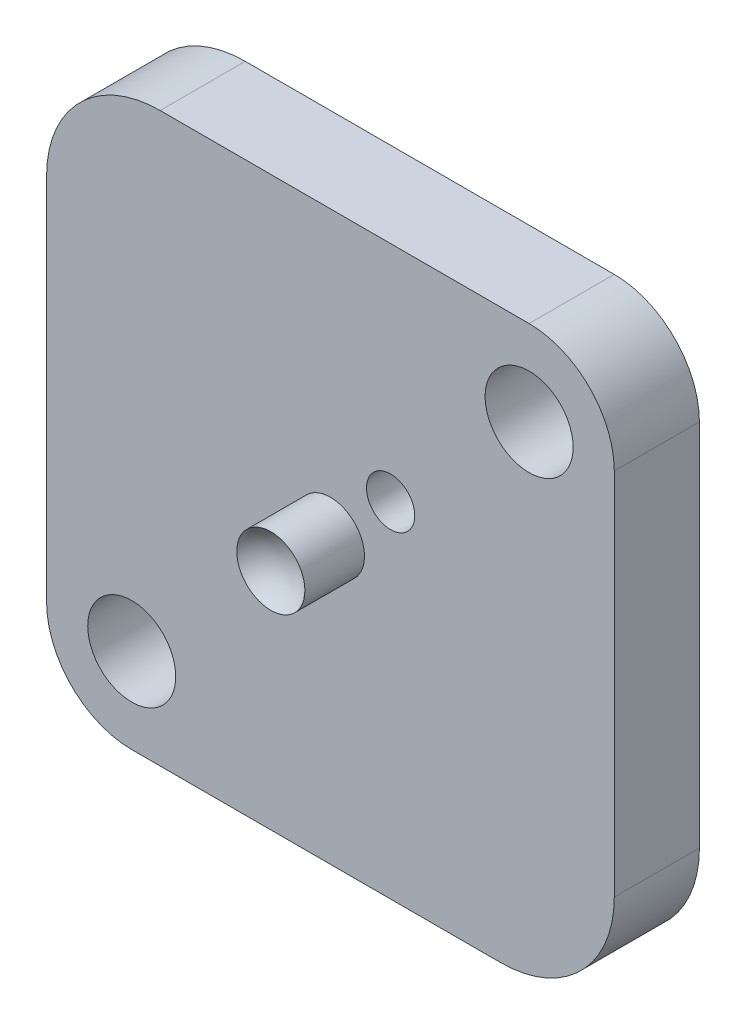
SolidWorks part; units mm, degrees
ref_plane "Front Plane" through (0, 0, 0) normal (0, 0, 1) x (1, 0, 0)
ref_plane "Top Plane" through (0, 0, 0) normal (0, 1, 0) x (1, 0, 0)
ref_plane "Right Plane" through (0, 0, 0) normal (1, 0, 0) x (0, 0, -1)
sketch "Sketch1" plane through (0, 0, 0) normal (0, 0, 1) x (1, 0, 0)
  line L1 (50, -50) -> (-50, -50)
  line L2 (50, -50) -> (50, 50)
  line L3 (50, 50) -> (-50, 50)
  line L4 (-50, -50) -> (-50, 50)
  line L5 (50, -50) -> (-50, 50) construction
  line L6 (50, 50) -> (-50, -50) construction
  point P0 (0, 0)
  dimension "D1" = 100
  dimension "D2" = 100
extrude "Boss-Extrude1" add sketch "Sketch1" along normal blind 15
sketch "Sketch2" plane through (0, 0, 15) normal (0, 0, 1) x (1, 0, 0)
  line L2 (50, -50) -> (50, 50) construction
  line L3 (50, 50) -> (-50, 50) construction
  line L4 (-50, 50) -> (50, -50) construction
  circle A0 centre (35, 35) radius 7.75
  circle A1 centre (-35, -35) radius 7.75
  dimension "D1" = 15.5
  dimension "D2" = 15
  dimension "D3" = 15
extrude "Cut-Extrude1" cut sketch "Sketch2" against normal through all
sketch "Sketch5" plane through (0, 0, 15) normal (0, 0, 1) x (1, 0, 0)
  circle A0 centre (0, 0) radius 6
  dimension "D1" = 12
extrude "Boss-Extrude6" add sketch "Sketch5" along normal blind 10.5
sketch "Sketch6" plane through (0, 0, 15) normal (0, 0, 1) x (1, 0, 0)
  line L0 (50, 50) -> (-50, -50) construction
  line L1 (-50, 50) -> (50, -50) construction
  circle A0 centre (10.6066, 10.6066) radius 4.25
  circle A1 centre (-10.6066, -10.6066) radius 4.25
  dimension "D2" = 15
  dimension "D1" = 8.5
extrude "Cut-Extrude3" cut sketch "Sketch6" against normal through all
fillet "Fillet1" radius 20 2 edges at (50, -50, 7.5) (-50, 50, 7.5)
fillet "Fillet2" radius 15 2 edges at (-50, -50, 7.5) (50, 50, 7.5)
dome "Dome2" faces to dome 1 distance 3 reverse direction yes elliptical dome no face at (6, 0, 25.5) parameters "D1"=3
